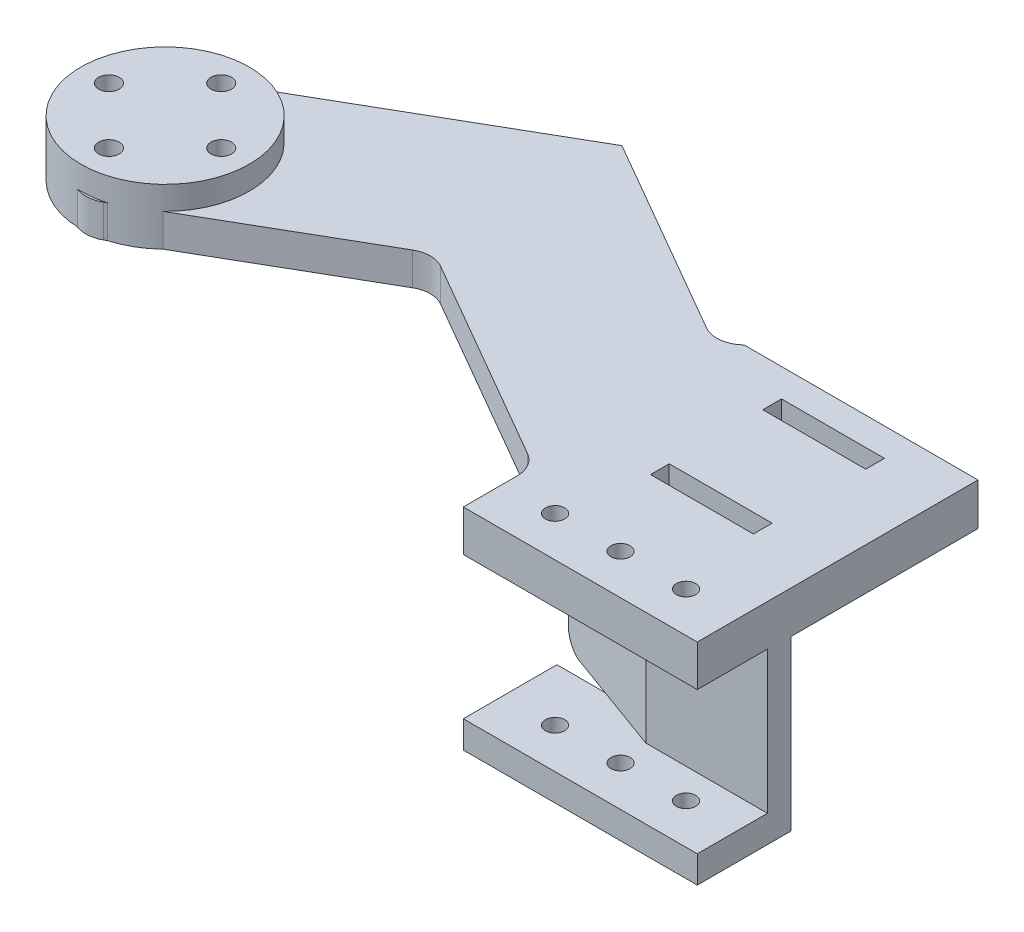
SolidWorks part; units mm, degrees
ref_plane "前视基准面" through (0, 0, 0) normal (0, 0, 1) x (1, 0, 0)
ref_plane "上视基准面" through (0, 0, 0) normal (0, 1, 0) x (1, 0, 0)
ref_plane "右视基准面" through (0, 0, 0) normal (1, 0, 0) x (0, 0, -1)
other "Configuration Table"
sketch "草图1" plane through (0, 0, 0) normal (0, 1, 0) x (1, 0, 0)
  line L1 (0, 0) -> (25, 0)
  line L2 (0, 0) -> (0, -10)
  line L3 (0, -10) -> (25, -10)
  line L4 (25, 0) -> (25, -10)
  dimension "D1" = 10
  dimension "D2" = 25
extrude "凸台-拉伸1" add sketch "草图1" along normal blind 22.5
sketch "草图2" plane through (0, 0, 10) normal (0, 0, 1) x (1, 0, 0)
  line L0 (0, 22.5) -> (0, 0) construction
  line L1 (0, 10.5) -> (6.5085, 10.5) construction
  line L2 (25, 22.5) -> (25, 0) construction
  line L3 (0, 18.1) -> (25, 18.1)
  line L4 (0, 18.1) -> (0, 2.9)
  line L5 (0, 2.9) -> (25, 2.9)
  line L6 (25, 18.1) -> (25, 2.9)
  line L7 (0, 18.1) -> (25, 2.9) construction
  line L8 (0, 22.5) -> (25, 22.5) construction
  point P4 (12.5, 10.5)
  point P12 (0, 11.25)
  dimension "D1" = 15.2
  dimension "D2" = 12
extrude "切除-拉伸1" cut sketch "草图2" against normal blind 7.5
sketch "草图4" plane through (0, 22.5, 0) normal (0, 1, 0) x (1, 0, 0)
  line L0 (12.5, -5.7) -> (19.5, -5.7) construction
  line L1 (12.5, -5.7) -> (5.5, -5.7) construction
  line L2 (0, -10) -> (25, -10) construction
  line L3 (25, 0) -> (0, 0) construction
  line L4 (12.5, -10) -> (12.5, -4.7527) construction
  circle A3 centre (12.5, -5.7) radius 1.03
  circle A4 centre (19.5, -5.7) radius 1.03
  circle A5 centre (5.5, -5.7) radius 1.03
  point P0 (12.5, -10)
  point P1 (12.5, -5.7)
  dimension "D3" = 7
  dimension "D2" = 7
  dimension "D1" = 5.7
extrude "切除-拉伸2" cut sketch "草图4" against normal through all both and the other way through all
sketch "草图5" plane through (0, 0, 0) normal (0, 0, -1) x (-1, 0, 0)
  line L0 (-25, 22.5) -> (0, 22.5) construction
  line L1 (-25, 22.5) -> (0, 22.5)
  line L2 (-25, 22.5) -> (-25, 18)
  line L3 (-25, 18) -> (0, 18)
  line L4 (0, 22.5) -> (0, 18)
  line L5 (-25, 22.5) -> (-25, 0) construction
  line L6 (0, 22.5) -> (0, 0) construction
  dimension "D1" = 4.5
extrude "凸台-拉伸2" add sketch "草图5" along normal blind 20
sketch "草图20" plane through (0, 0, 0) normal (0, 1, 0) x (1, 0, 0)
  line L0 (12.5, -10) -> (12.5, 20) construction
  line L1 (0, -10) -> (25, -10) construction
  line L2 (0, 20) -> (25, 20) construction
sketch "草图6" plane through (0, 22.5, 0) normal (0, 1, 0) x (1, 0, 0)
  line L0 (0, 10) -> (25, 10) construction
  line L1 (0, 20) -> (0, -10) construction
  line L2 (25, -10) -> (25, 20) construction
  line L3 (0, 20) -> (25, 20) construction
  line L4 (12.5, -10) -> (12.5, -7.6427) construction
  line L5 (7, 17) -> (18, 17)
  line L6 (7, 17) -> (7, 15)
  line L7 (7, 15) -> (18, 15)
  line L8 (18, 17) -> (18, 15)
  line L9 (7, 17) -> (18, 15) construction
  line L10 (7, 15) -> (18, 17) construction
  line L11 (7, 5) -> (18, 5)
  line L12 (7, 5) -> (7, 3)
  line L13 (7, 3) -> (18, 3)
  line L14 (18, 5) -> (18, 3)
  line L15 (7, 5) -> (18, 3) construction
  line L16 (7, 3) -> (18, 5) construction
  point P8 (12.5, 16)
  point P9 (12.5, 4)
  point P10 (12.5, 16)
  point P15 (12.5, 4)
  dimension "D1" = 10
  dimension "D2" = 6
  dimension "D3" = 6
  dimension "D4" = 2
  dimension "D5" = 11
  dimension "D6" = 11
  dimension "D7" = 2
extrude "切除-拉伸3" cut sketch "草图6" against normal up to surface (4.5 mm away) up to face at (12.5, 18, -10)
sketch "草图9" plane through (0, 0, 0) normal (-1, 0, 0) x (0, 0, 1)
  line L0 (2.5, 18.1) -> (2.5, 22.5) construction
  line L1 (-20, 22.5) -> (10, 22.5) construction
sketch "草图14" plane through (25, 0, 0) normal (1, 0, 0) x (0, 0, -1)
  line L0 (-2.5, 18.1) -> (-2.5, 22.5) construction
  line L1 (-10, 22.5) -> (20, 22.5) construction
sketch "草图15" plane through (0, 22.5, 0) normal (0, 1, 0) x (1, 0, 0)
  line L2 (25, -2.5) -> (75, -2.5) construction
  line L8 (12.5, 20) -> (12.5, -10) construction
  line L9 (0, -10) -> (25, -10) construction
  line L10 (0, 17.5) -> (0, -2.5)
  line L11 (-50, 17.5) -> (-50, -2.5)
  line L12 (-24.9672, 31.9148) -> (-50, 17.5)
  line L13 (0, 17.5) -> (-24.9672, 31.9148)
  line L14 (-25, 11.9338) -> (-50, -2.5)
  line L15 (0, -2.5) -> (-25, 11.9338)
  dimension "D1" = 50
extrude "凸台-拉伸3" add sketch "草图15" against normal blind 3.5
sketch "草图16" plane through (0, 19, 0) normal (0, -1, 0) x (1, 0, 0)
  line L0 (12.5, 10) -> (12.5, -20) construction
  circle A1 centre (-49.6554, -7.7821) radius 9
  point P12 (-49.6554, -7.7821)
  point P13 (-49.6554, -7.7821)
extrude "凸台-拉伸4" add sketch "草图16" against normal blind 6
sketch "草图17" plane through (0, 19, 0) normal (0, -1, 0) x (1, 0, 0)
  line L0 (12.5, 10) -> (12.5, -20) construction
  circle A5 centre (-49.6554, -7.7821) radius 6 construction
  circle A6 centre (-55.6554, -7.7821) radius 1.1
  circle A7 centre (-43.6554, -7.7821) radius 1.1
  circle A8 centre (-49.6554, -1.7821) radius 1.1
  circle A9 centre (-49.6554, -13.7821) radius 1.1
extrude "切除-拉伸4" cut sketch "草图17" against normal up to next
sketch "草图18" plane through (25, 0, 0) normal (1, 0, 0) x (0, 0, -1)
  line L0 (-2.5, 2.9) -> (0, 2.9) construction
  line L1 (0, 18) -> (0, 0) construction
  line L2 (0, 18) -> (-2.5, 18) construction
  line L3 (-2.5, 2.9) -> (-2.5, 18.1) construction
  point P6 (0, 2.9)
  point P12 (0, 18)
sketch "草图19" plane through (0, 0, 0) normal (0, 0, -1) x (-1, 0, 0)
  line L0 (-25, 18) -> (0, 18) construction
  line L1 (-25, 2.9) -> (0, 2.9)
  line L2 (-25, 2.9) -> (-25, 18) construction
  line L3 (-25, 18) -> (0, 18)
  line L4 (0, 2.9) -> (0, 18)
  line L5 (-12, 2.9) -> (-12, 18)
  line L6 (0, 18) -> (0, 0) construction
  line L8 (-25, 18) -> (-12, 18)
  line L9 (-25, 18) -> (-25, 2.9) construction
  line L10 (-25, 2.9) -> (-12, 2.9)
  line L11 (-12, 18) -> (-12, 2.9)
  line M3 (0, 18) -> (-25, 18)
  line M6 (0, 0) -> (0, 18)
  dimension "D1" = 12
extrude "切除-拉伸5" cut sketch "草图19" against normal up to next contours L5 L1 M6 M3 region at (6, 10.45, 0)
fillet "圆角7" radius 3 4 edges at (0, 20.75, -17.5) (0, 20.75, 2.5) (-25, 20.75, -11.9338) (-50, 20.75, 2.5)
sketch "草图21" plane through (0, 2.9, 0) normal (0, 1, 0) x (1, 0, 0)
  line L0 (12, -2.5) -> (12, 0)
  line L1 (12, 0) -> (0, 0) construction
  line L2 (12, 0) -> (-6.7939, 6.8404)
  line L3 (12, -2.5) -> (-8.1413, 4.8308)
  line L4 (-8.1413, 4.8308) -> (-7.5973, 4.6328)
  line L5 (-7.5973, 4.6328) -> (-6.7939, 6.8404)
  line M12 (12, -2.5) -> (12, 0)
  line M13 (12, 0) -> (0, 0)
  dimension "D1" = 20
  dimension "D2" = 20
extrude "凸台-拉伸6" add sketch "草图21" along normal up to surface (16.1 mm away) contours L5 L3 L2 M13 | L3 M12 M13 region at (9.7104, 2.9, 0.8333) region at (0.808, 2.9, -2.9037) up to face at (-55.6554, 19, -6.6821)
sketch "草图22" plane through (1.4037, 0, -3.8567) normal (0.342, 0, -0.9397) x (-0.9397, 0, -0.342)
  line L1 (8.7237, 2.9) -> (1.7237, 2.9)
  line L2 (8.7237, 2.9) -> (8.7237, 7.9)
  line L3 (8.7237, 7.9) -> (1.7237, 7.9)
  line L4 (1.7237, 2.9) -> (1.7237, 7.9)
  dimension "D1" = 5
  dimension "D2" = 7
extrude "切除-拉伸6" cut sketch "草图22" against normal up to next
fillet "圆角8" radius 2 3 edges at (-7.1956, 7.9, -5.7366) (-0.6177, 7.9, -3.3425) (-0.6177, 2.9, -3.3425)
